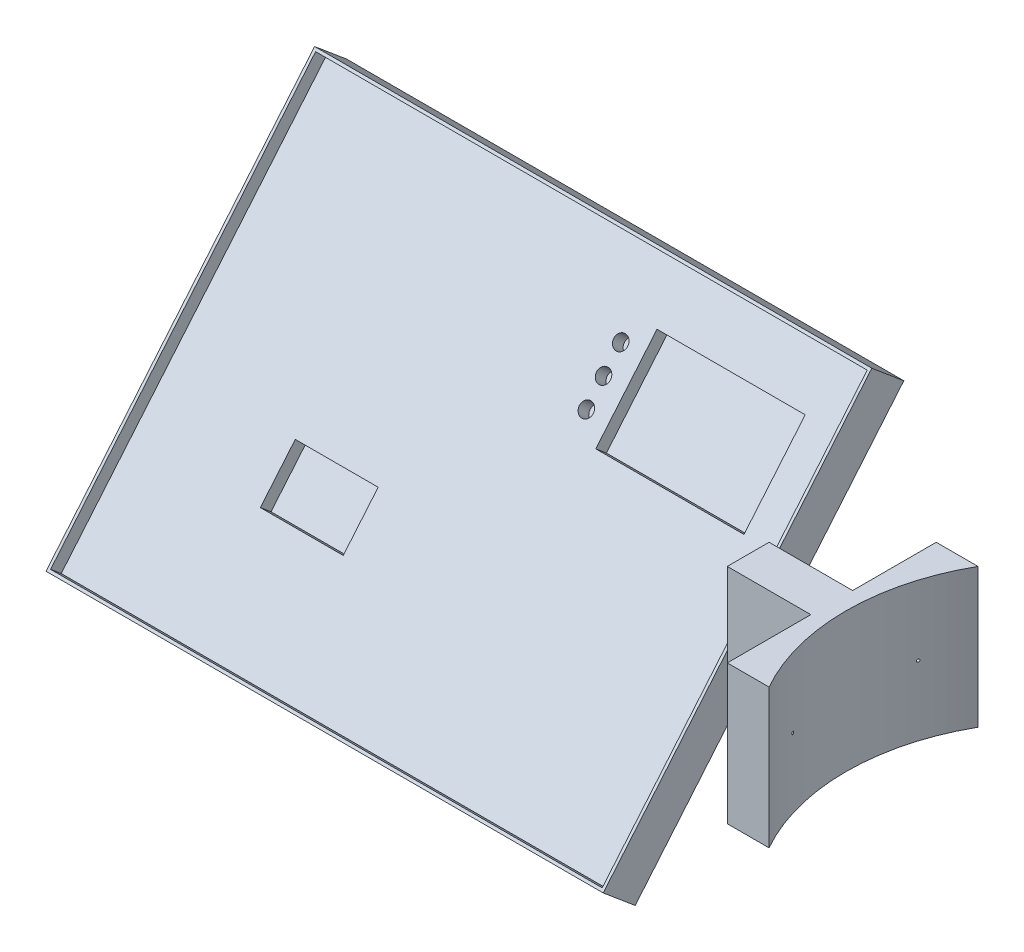
SolidWorks part; units mm, degrees
ref_plane "Plan de face" through (0, 0, 0) normal (0, 0, 1) x (1, 0, 0)
ref_plane "Plan de dessus" through (0, 0, 0) normal (0, 1, 0) x (1, 0, 0)
ref_plane "Plan de droite" through (0, 0, 0) normal (1, 0, 0) x (0, 0, -1)
sketch "Esquisse1" plane through (0, 0, 0) normal (0, 1, 0) x (1, 0, 0)
  line L0 (30, 15) -> (30, 75)
  line L1 (30, -75) -> (60, -75)
  line L2 (30, -75) -> (30, -15)
  line L3 (30, 75) -> (60, 75)
  line L5 (30, -75) -> (40.2082, 0) construction
  line L6 (30, 75) -> (40.2082, 0) construction
  line L7 (-30, -15) -> (30, -15)
  line L8 (-30, -15) -> (-30, 15)
  line L9 (-30, 15) -> (30, 15)
  line L11 (-30, -15) -> (30, 15) construction
  line L12 (-30, 15) -> (30, -15) construction
  arc A0 (60, 75) -> (60, -75) centre (192.2082, 0) ccw
  point P2 (40.2082, 0)
  point P3 (0, 0)
  dimension "D1" = 304
  dimension "D2" = 150
  dimension "D3" = 30
  dimension "D4" = 60
  dimension "D5" = 30
  dimension "D6" = 30
extrude "Boss.-Extru.1" add sketch "Esquisse1" along normal blind 100
sketch "Esquisse2" plane through (-30, 0, 0) normal (-1, 0, 0) x (0, 0, 1)
  line L0 (15, 100) -> (-15, 0) construction
  line L1 (-15, 100) -> (15, 0) construction
  line L2 (-93.7673, 161.7475) -> (94.1099, -62.1558) construction
  line L3 (0, 50) -> (0, 100) construction
  line L4 (-15, 100) -> (15, 100) construction
  line L5 (-111.739, 152.0509) -> (81.0973, -77.7624)
  line L6 (0, 50) -> (-15.3209, 37.1442) construction
  line L7 (-111.739, 152.0509) -> (-88.7577, 171.3345)
  line L8 (-88.7577, 171.3345) -> (104.0786, -58.4788)
  line L9 (104.0786, -58.4788) -> (81.0973, -77.7624)
  point P10 (0, 50)
  dimension "D1" = 40
  dimension "D2" = 20
  dimension "D3" = 300
  dimension "D4" = 30
extrude "Boss.-Extru.2" add sketch "Esquisse2" along normal blind 400
sketch "Esquisse3" plane through (0, 27.0867, 32.2806) normal (0, 0.6428, 0.766) x (1, 0, 0)
  line L1 (-430, 188.3022) -> (-30, 188.3022)
  line L2 (-430, 188.3022) -> (-430, -111.6978)
  line L3 (-430, -111.6978) -> (-30, -111.6978)
  line L4 (-30, 188.3022) -> (-30, -111.6978)
  line L5 (-428, -109.6978) -> (-32, -109.6978)
  line L6 (-428, -109.6978) -> (-428, 186.3022)
  line L7 (-428, 186.3022) -> (-32, 186.3022)
  line L8 (-32, -109.6978) -> (-32, 186.3022)
  line L9 (-428, -109.6978) -> (-32, 186.3022) construction
  line L10 (-428, 186.3022) -> (-32, -109.6978) construction
  line L11 (-167.1753, 81.5044) -> (-60.7753, 81.5044)
  line L12 (-167.1753, 81.5044) -> (-167.1753, 149.9044)
  line L13 (-167.1753, 149.9044) -> (-60.7753, 149.9044)
  line L14 (-60.7753, 81.5044) -> (-60.7753, 149.9044)
  line L15 (-167.1753, 81.5044) -> (-60.7753, 149.9044) construction
  line L16 (-167.1753, 149.9044) -> (-60.7753, 81.5044) construction
  line L17 (-336.3779, 9.1308) -> (-276.8779, 9.1308)
  line L18 (-336.3779, 9.1308) -> (-336.3779, -29.8692)
  line L19 (-336.3779, -29.8692) -> (-276.8779, -29.8692)
  line L20 (-276.8779, 9.1308) -> (-276.8779, -29.8692)
  circle A0 centre (-183.5791, 134.9044) radius 5
  circle A1 centre (-183.5791, 115.7044) radius 5
  circle A2 centre (-183.5791, 96.5044) radius 5
  point P6 (-230, 38.3022)
  point P12 (-230, 188.3022)
  point P13 (-430, 38.3022)
  point P14 (-113.9753, 115.7044)
  point P28 (0, 0)
  point P29 (0, 0)
  dimension "D9" = 10
  dimension "D10" = 10
  dimension "D11" = 10
  dimension "D1" = 400
  dimension "D2" = 300
  dimension "D3" = 396
  dimension "D4" = 296
  dimension "D5" = 106.4
  dimension "D6" = 68.4
  dimension "D7" = 59.5
  dimension "D8" = 39
  dimension "D12" = 15
  dimension "D13" = 15
extrude "Enlèv. mat.-Extru.1" cut sketch "Esquisse3" against normal blind 10 contours L5 L8 L7 L6 L14 L11 L12 L13 region at (-236.3095, 53.0849, 10.4655)
extrude "Enlèv. mat.-Extru.2" cut sketch "Esquisse3<3>" against normal blind 20 contours L11 L14 L13 L12 | L18 L17 L20 L19 | A2 | A1 | A0 region at (-113.9753, 115.7214, -42.0927)
sketch "Esquisse3<3>" plane through (0, 27.0867, 32.2806) normal (0, 0.6428, 0.766) x (1, 0, 0) same geometry as "Esquisse3"
sketch "Esquisse4" plane through (30, 0, 0) normal (-1, 0, 0) x (0, 0, 1)
  line L0 (-75, 50) -> (75, 50) construction
  line L1 (-75, 100) -> (-75, 0) construction
  line L2 (75, 100) -> (75, 0) construction
  circle A0 centre (-45, 50) radius 1
  circle A1 centre (45, 50) radius 1
  dimension "D1" = 2
  dimension "D2" = 2
  dimension "D3" = 30
  dimension "D4" = 30
extrude "Enlèv. mat.-Extru.3" cut sketch "Esquisse4" against normal blind 60
